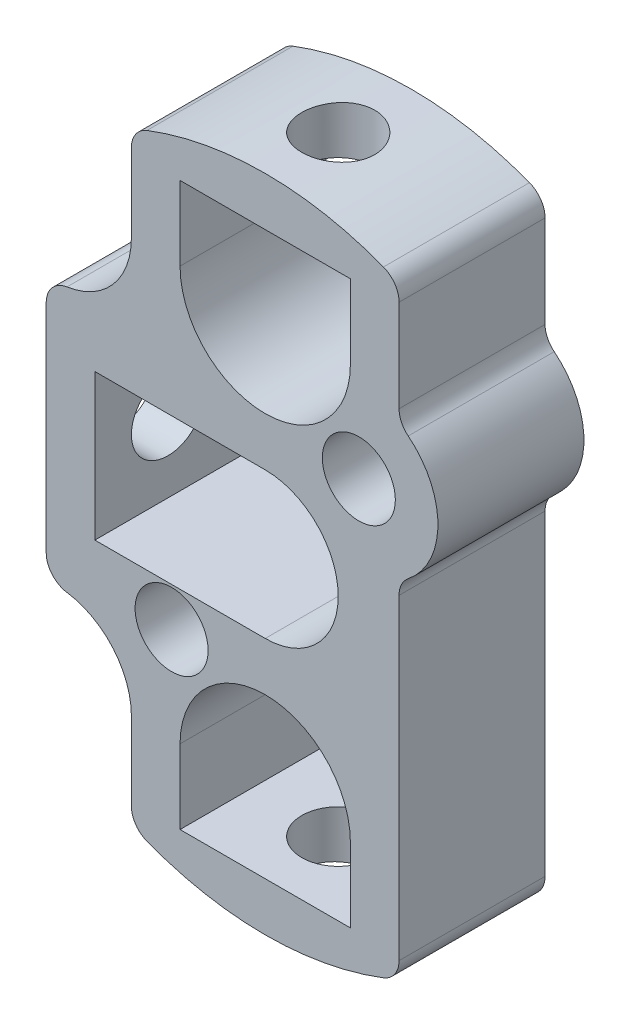
SolidWorks part; units mm, degrees
ref_plane "Plan de face" through (0, 0, 0) normal (0, 0, 1) x (1, 0, 0)
ref_plane "Plan de dessus" through (0, 0, 0) normal (0, 1, 0) x (1, 0, 0)
ref_plane "Plan de droite" through (0, 0, 0) normal (1, 0, 0) x (0, 0, -1)
sketch "Esquisse1" plane through (0, 0, 0) normal (0, 0, 1) x (1, 0, 0)
  line L0 (0, -1000) -> (0, 49000) construction
  line L1 (-3.5, 11.55) -> (3.5, 11.55)
  line L2 (-1000, 0) -> (49000, 0) construction
  line L3 (-3.5, -11.55) -> (3.5, -11.55)
  line L4 (-3.5, 8.5) -> (-3.5, 11.55)
  line L5 (3.5, 8.5) -> (3.5, 11.55)
  line L6 (3.5, -8.5) -> (3.5, -11.55)
  line L7 (-3.5, -8.5) -> (-3.5, -11.55)
  line L8 (-2.0275, -5.6471) -> (-5.1962, -3) construction
  line L9 (0, -3) -> (-7, -3)
  line L10 (0, -3) -> (0, 3) construction
  line L11 (0, 3) -> (-7, 3)
  line L12 (-7, -3) -> (-7, 3)
  line L13 (0, 0) -> (-32055.7157, -38372.2698) construction
  line L14 (5.5, -12.3836) -> (5.5, 12.3836) construction
  line L15 (-9, 4.4479) -> (-9, -4.4479)
  line L16 (-5.5, 11.7155) -> (-5.5, 8.5)
  line L17 (-5.5, -11.7155) -> (-5.5, -8.5)
  line L18 (5.5, 11.7155) -> (5.5, 7.9247)
  line L19 (5.5, 1.2847) -> (5.5, -11.7155)
  circle A0 centre (0, 0) radius 13.55 construction
  circle A1 centre (0, 0) radius 3 construction
  circle A2 centre (0, 0) radius 6 construction
  arc A3 (-3.5, 8.5) -> (3.5, 8.5) centre (0, 8.5) ccw
  arc A4 (-3.5, -8.5) -> (3.5, -8.5) centre (0, -8.5) cw
  arc A5 (0, 3) -> (0, -3) centre (0, 0) cw
  circle A6 centre (-3.8467, -4.6047) radius 1.5
  circle A7 centre (3.8467, 4.6047) radius 1.5
  arc A8 (-5.5, 8.5) -> (-8.1454, 5.4373) centre (-8.5956, 8.5) cw
  arc A9 (-4.8586, 12.649) -> (4.8586, 12.649) centre (0, 0) cw
  arc A10 (-4.8586, -12.649) -> (4.8586, -12.649) centre (0, 0) ccw
  arc A11 (-5.5, -8.5) -> (-8.1454, -5.4373) centre (-8.5956, -8.5) ccw
  arc A12 (-8.1454, -5.4373) -> (-9, -4.4479) centre (-8, -4.4479) cw
  arc A13 (-9, 4.4479) -> (-8.1454, 5.4373) centre (-8, 4.4479) cw
  circle A14 centre (3.8467, 4.6047) radius 3.25 construction
  arc A15 (5.8757, 7.1435) -> (5.8757, 2.0658) centre (3.8467, 4.6047) cw
  arc A16 (5.8757, 2.0658) -> (5.5, 1.2847) centre (6.5, 1.2847) ccw
  arc A17 (5.5, 7.9247) -> (5.8757, 7.1435) centre (6.5, 7.9247) ccw
  arc A18 (5.5, 11.7155) -> (4.8586, 12.649) centre (4.5, 11.7155) ccw
  arc A19 (-5.5, 11.7155) -> (-4.8586, 12.649) centre (-4.5, 11.7155) cw
  arc A20 (4.8586, -12.649) -> (5.5, -11.7155) centre (4.5, -11.7155) ccw
  arc A21 (-4.8586, -12.649) -> (-5.5, -11.7155) centre (-4.5, -11.7155) cw
  point P4 (0, 13.55)
  point P9 (0, 11.55)
  point P21 (0, 5)
  point P22 (0, 3)
  point P41 (6.8467, 0)
  point P48 (-9, 0)
  point P50 (-9, -5.4309)
  point P53 (-9, 5.4309)
  point P56 (5.5, 0)
  point P61 (5.5, 1.8066)
  point P64 (5.5, 7.4027)
  point P69 (-5.5, 12.3836)
  point P75 (-5.5, -12.3836)
  dimension "D1" = 27.1
  dimension "D2" = 6
  dimension "D4" = 12
  dimension "D6" = 7
  dimension "D7" = 2
  dimension "D8" = 3
  dimension "D10" = 3
  dimension "D12" = 1
  dimension "D14" = 6.5
  dimension "D15" = 1
  dimension "D16" = 1
  dimension "D3" = 2
  dimension "D5" = 7
  dimension "D9" = 2
  dimension "D11" = 2
  dimension "D13" = 2
extrude "Boss.-Extru.1" add sketch "Esquisse1" along normal blind 6 contours A3 L4 L1 L5 A1 L7 A4 L6 L3 region at (-8.5182, 4.8956, 0)
sketch "Esquisse2" plane through (0, 11.55, 0) normal (0, -1, 0) x (1, 0, 0)
  line L0 (-3.5, 6) -> (3.5, 0) construction
  circle A0 centre (0, 3) radius 1.5
  dimension "D1" = 3
extrude "Enlèv. mat.-Extru.1" cut sketch "Esquisse2" against normal through all
mirror "Symétrie1" about plane through (0, 0, 0) normal (0, 1, 0) of "Enlèv. mat.-Extru.1"
sketch "Esquisse3" plane through (-7, 0, 0) normal (1, 0, 0) x (0, 0, -1)
  line L0 (-6, 3) -> (0, -3) construction
  circle A0 centre (-3, 0) radius 1.5
  dimension "D1" = 3
extrude "Enlèv. mat.-Extru.2" cut sketch "Esquisse3" against normal through all
